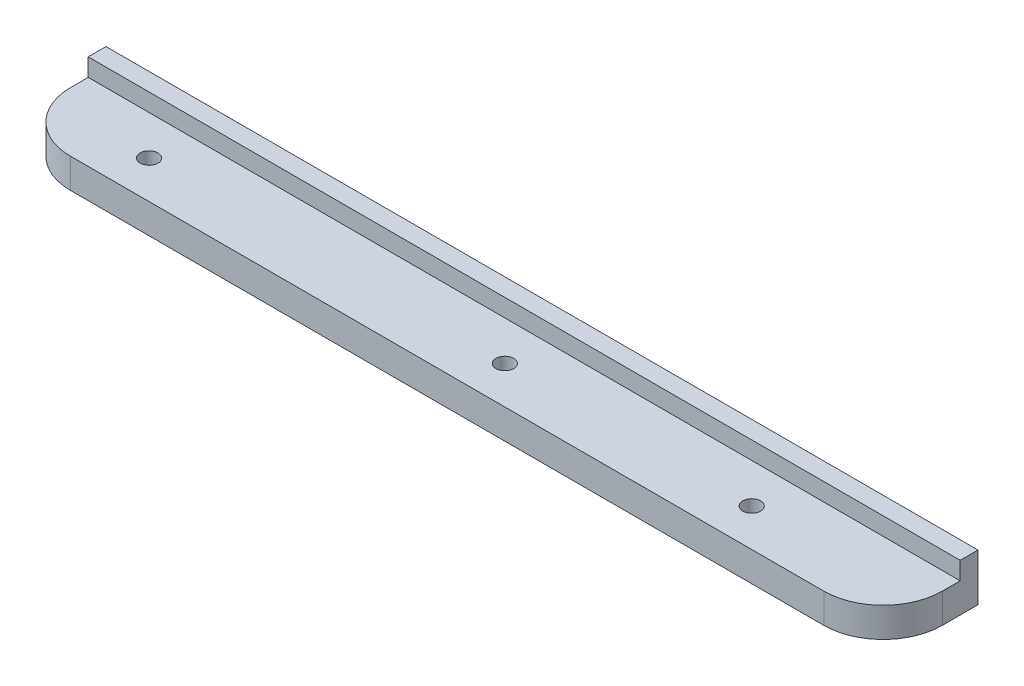
SolidWorks part; units mm, degrees
ref_plane "Front Plane" through (0, 0, 0) normal (0, 0, 1) x (1, 0, 0)
ref_plane "Top Plane" through (0, 0, 0) normal (0, 1, 0) x (1, 0, 0)
ref_plane "Right Plane" through (0, 0, 0) normal (1, 0, 0) x (0, 0, -1)
sketch "Sketch2" plane through (0, 0, 0) normal (0, 1, 0) x (1, 0, 0)
  line L0 (79.8329, 11.2298) -> (51.3329, 11.2298)
  line L1 (-67.1671, 37.2298) -> (79.8329, 37.2298)
  line L2 (-67.1671, 37.2298) -> (-67.1671, 11.2298)
  line L3 (51.3329, 11.2298) -> (9.7229, 11.2298)
  line L4 (79.8329, 37.2298) -> (79.8329, 11.2298)
  line L5 (9.7229, 11.2298) -> (-67.1671, 11.2298)
  line L6 (51.3329, 11.2298) -> (-50.2671, 11.2298)
  line L7 (-50.2671, 11.2298) -> (-50.2671, 17.5798)
  line L8 (-50.2671, 17.5798) -> (9.7229, 17.5798)
  line L9 (9.7229, 17.5798) -> (51.3329, 17.5798)
  circle A0 centre (9.7229, 17.5798) radius 1.5
  circle A1 centre (51.3329, 17.5798) radius 1.5
  circle A2 centre (-50.2671, 17.5798) radius 1.5
  dimension "D6" = 3
  dimension "D7" = 3
  dimension "D8" = 3
  dimension "D1" = 147
  dimension "D2" = 26
  dimension "D3" = 28.5
  dimension "D4" = 101.6
  dimension "D5" = 41.61
extrude "Boss-Extrude1" add sketch "Sketch2" along normal blind 5 contours A2 L5 L3 L0 L4 L1 L2 A0 A1 region at (6.3482, 0, -24.2669)
sketch "Sketch3" plane through (0, 5, 0) normal (0, 1, 0) x (1, 0, 0)
  line L0 (-67.1671, 37.2298) -> (-67.1671, 11.2298) construction
  line L1 (-67.1671, 24.2298) -> (79.8329, 24.2298)
  line L2 (-67.1671, 24.2298) -> (-67.1671, 27.2298)
  line L3 (-67.1671, 27.2298) -> (79.8329, 27.2298)
  line L4 (79.8329, 24.2298) -> (79.8329, 27.2298)
  line L5 (79.8329, 37.2298) -> (79.8329, 11.2298) construction
  dimension "D1" = 3
extrude "Boss-Extrude2" add sketch "Sketch3" along normal blind 3
fillet "Fillet1" radius 10 2 edges at (-67.1671, 2.5, -11.2298) (-67.1671, 2.5, -37.2298)
fillet "Fillet2" radius 10 2 edges at (79.8329, 2.5, -11.2298) (79.8329, 2.5, -37.2298)
sketch "Sketch4" plane through (0, 0, -37.2298) normal (0, 0, -1) x (-1, 0, 0)
  line L1 (111.4458, -45.7652) -> (98.7713, -45.7652)
  line L2 (111.4458, -45.7652) -> (111.4458, -41.9561)
  line L3 (111.4458, -41.9561) -> (98.7713, -41.9561)
  line L4 (98.7713, -45.7652) -> (98.7713, -41.9561)
  line L5 (98.7713, -41.9561) -> (-95.4975, -41.9561)
  line L6 (98.7713, -41.9561) -> (98.7713, 30.7698)
  line L7 (98.7713, 30.7698) -> (-95.4975, 30.7698)
  line L8 (-95.4975, -41.9561) -> (-95.4975, 30.7698)
  line M1 (57.1671, 5) -> (-69.8329, 5)
  line M2 (-69.8329, 5) -> (-69.8329, 0)
  line M3 (-69.8329, 0) -> (57.1671, 0)
  line M4 (57.1671, 0) -> (57.1671, 5)
extrude "Cut-Extrude1" cut sketch "Sketch4" against normal blind 10 contours M4 M1 M2 M3 | L8 L5 L6 L7 M1 M4 M3 M2 region at (-2.0119, -5.974, -37.2298) region at (6.3329, 2.5, -37.2298)
sketch "Sketch5" plane through (0, 5, 0) normal (0, 1, 0) x (1, 0, 0)
  line L0 (-50.2671, 17.5798) -> (-67.1671, 17.5798)
  line L1 (-67.1671, 17.5798) -> (9.7229, 17.5798)
  line L2 (9.7229, 17.5798) -> (51.3329, 17.5798)
  line L3 (79.8329, 27.2298) -> (-67.1671, 27.2298) construction
  dimension "D1" = 16.9
  dimension "D2" = 59.99
  dimension "D3" = 41.61
  dimension "D4" = 9.65
